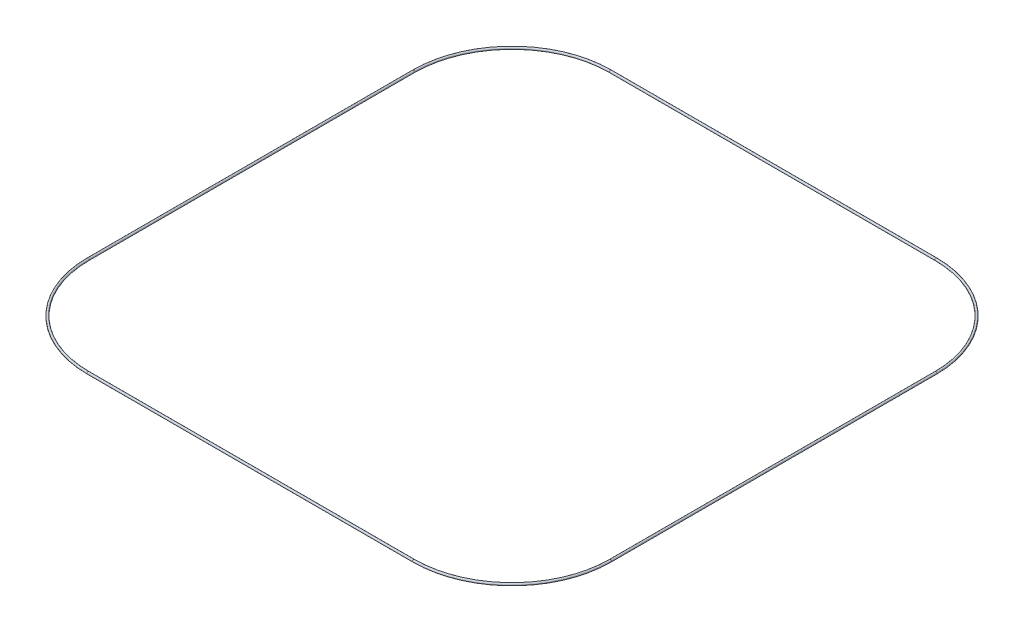
SolidWorks part; units mm, degrees
material "5052-O"
ref_plane "Front Plane" through (0, 0, 0) normal (0, 0, 1) x (1, 0, 0)
ref_plane "Top Plane" through (0, 0, 0) normal (0, 1, 0) x (1, 0, 0)
ref_plane "Right Plane" through (0, 0, 0) normal (1, 0, 0) x (0, 0, -1)
sketch "Sketch1" plane through (0, 0, 0) normal (0, 1, 0) x (1, 0, 0)
  line L1 (139.7, 0) -> (601.98, 0)
  line L2 (0, 139.7) -> (0, 601.98)
  line L3 (139.7, 741.68) -> (601.98, 741.68)
  line L4 (741.68, 139.7) -> (741.68, 601.98)
  arc A0 (0, 139.7) -> (139.7, 0) centre (139.7, 139.7) ccw
  arc A1 (601.98, 0) -> (741.68, 139.7) centre (601.98, 139.7) ccw
  arc A2 (741.68, 601.98) -> (601.98, 741.68) centre (601.98, 601.98) ccw
  arc A3 (139.7, 741.68) -> (0, 601.98) centre (139.7, 601.98) ccw
  point P9 (0, 0)
  point P13 (741.68, 0)
  point P18 (0, 741.68)
  dimension "D3" = 139.7
  dimension "D1" = 741.68
  dimension "D2" = 741.68
ref_plane "Plane2" through (0, 0, -139.7) normal (0, 0, -1) x (-1, 0, 0)
sketch "Sketch3" plane through (0, 0, -139.7) normal (0, 0, -1) x (-1, 0, 0)
  circle A0 centre (0, 0) radius 1.5875
  dimension "D1" = 3.175
sweep "Sweep2" add profiles "Sketch3" path "Sketch1"
